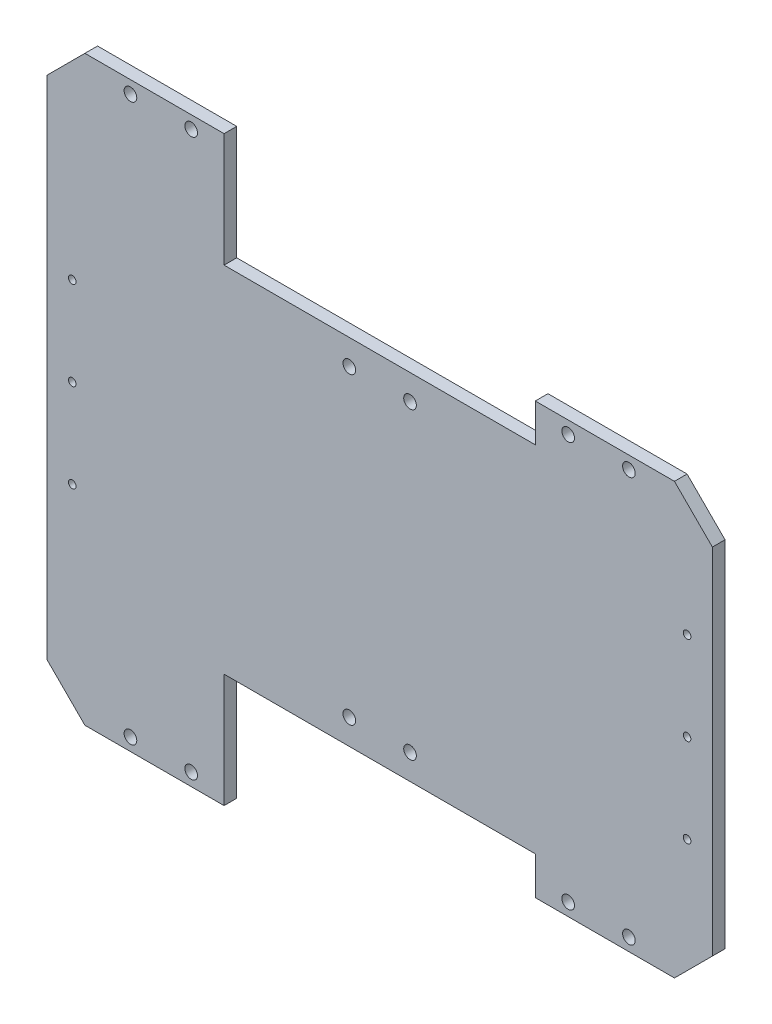
SolidWorks part; units mm, degrees
ref_plane "前视基准面" through (0, 0, 0) normal (0, 0, 1) x (1, 0, 0)
ref_plane "上视基准面" through (0, 0, 0) normal (0, 1, 0) x (1, 0, 0)
ref_plane "右视基准面" through (0, 0, 0) normal (1, 0, 0) x (0, 0, -1)
ref_plane "基准面4" through (0, 0, 5) normal (0, 0, 1) x (1, 0, 0)
sketch "草图1" plane through (0, 0, 5) normal (0, 0, 1) x (1, 0, 0)
  line L3 (50.93, -100) -> (50.93, 40)
  line L4 (50.93, 40) -> (35.93, 55)
  line L5 (35.93, 55) -> (-19.07, 55)
  line L6 (-19.07, 55) -> (-19.07, 40)
  line L7 (-19.07, 40) -> (-142.07, 40)
  line L8 (-142.07, 40) -> (-142.07, 85)
  line L9 (-142.07, 85) -> (-197.07, 85)
  line L10 (-197.07, 85) -> (-212.07, 70)
  line L11 (-212.07, 70) -> (-212.07, -130)
  line L53 (-197.07, -145) -> (-212.07, -130)
  line L54 (-142.07, -145) -> (-197.07, -145)
  line L55 (-142.07, -100) -> (-142.07, -145)
  line L56 (-19.07, -100) -> (-142.07, -100)
  line L57 (-19.07, -115) -> (-19.07, -100)
  line L58 (35.93, -115) -> (-19.07, -115)
  line L59 (50.93, -100) -> (35.93, -115)
  circle A0 centre (-179.07, 80) radius 2.5
  circle A3 centre (-6.07, 50) radius 2.5
  circle A6 centre (-155.07, 80) radius 2.5
  circle A8 centre (-92.57, 30) radius 2.5
  circle A9 centre (-68.57, 30) radius 2.5
  circle A10 centre (17.93, 50) radius 2.5
  circle A30 centre (-202.07, 5) radius 1.5
  circle A31 centre (-202.07, -30) radius 1.5
  circle A34 centre (40.93, -30) radius 1.5
  circle A35 centre (40.93, 5) radius 1.5
  circle A36 centre (40.93, -65) radius 1.5
  circle A37 centre (-202.07, -65) radius 1.5
  circle A40 centre (17.93, -110) radius 2.5
  circle A41 centre (-68.57, -90) radius 2.5
  circle A42 centre (-92.57, -90) radius 2.5
  circle A43 centre (-155.07, -140) radius 2.5
  circle A44 centre (-6.07, -110) radius 2.5
  circle A45 centre (-179.07, -140) radius 2.5
  point P21 (0, 0)
  dimension "D3" = 33
  dimension "D4" = 5
  dimension "D5" = 45
  dimension "D7" = 24
  dimension "D8" = 5
  dimension "D9" = 5
  dimension "D10" = 5
  dimension "D11" = 5
  dimension "D12" = 24
  dimension "D13" = 5
  dimension "D6" = 24
  dimension "D19" = 15
  dimension "D22" = 5
  dimension "D24" = 35
  dimension "D20" = 13
  dimension "D23" = 263
  dimension "D16" = 33
  dimension "D2" = 135
  dimension "D14" = 135
  dimension "D17" = 13
  dimension "D18" = 123
  dimension "D21" = 15
  dimension "D26" = 15
extrude "凸台-拉伸1" add sketch "草图1" along normal blind 5
